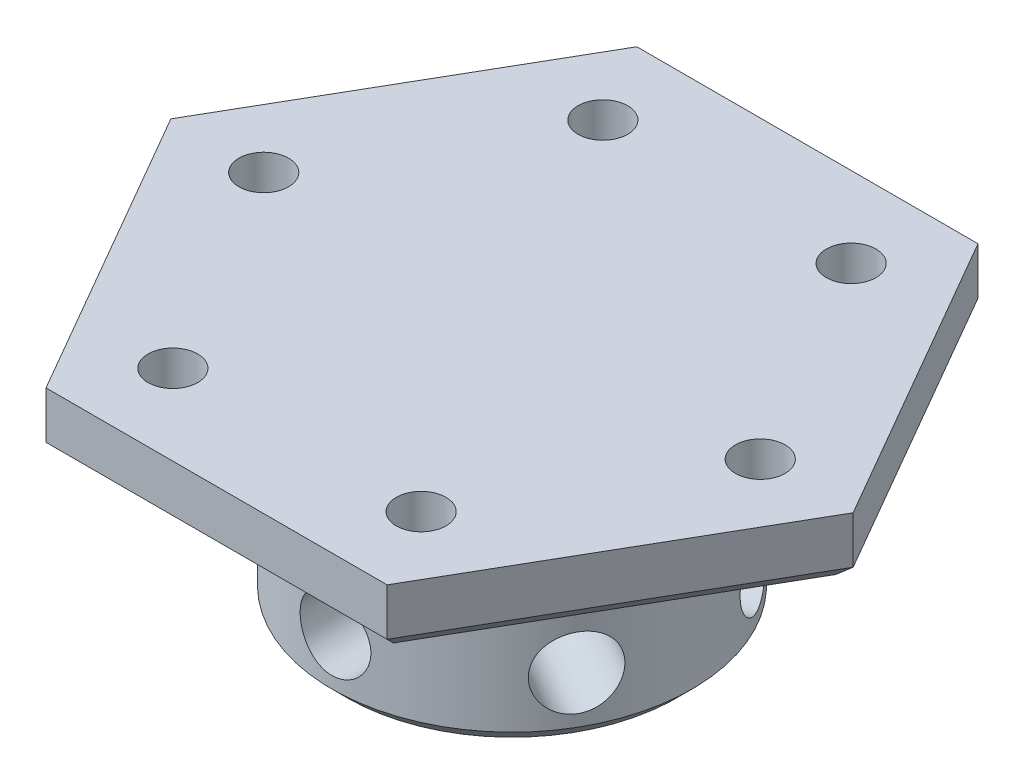
SolidWorks part; units mm, degrees
ref_plane "前视基准面" through (0, 0, 0) normal (0, 0, 1) x (1, 0, 0)
ref_plane "上视基准面" through (0, 0, 0) normal (0, 1, 0) x (1, 0, 0)
ref_plane "右视基准面" through (0, 0, 0) normal (1, 0, 0) x (0, 0, -1)
other "Configuration Table"
sketch "草图1" plane through (0, 0, 0) normal (0, 1, 0) x (1, 0, 0)
  line L1 (13.7409, 0) -> (6.8705, 11.9)
  line L2 (6.8705, 11.9) -> (-6.8705, 11.9)
  line L3 (-6.8705, 11.9) -> (-13.7409, 0)
  line L4 (-13.7409, 0) -> (-6.8705, -11.9)
  line L5 (-6.8705, -11.9) -> (6.8705, -11.9)
  line L6 (6.8705, -11.9) -> (13.7409, 0)
  circle A0 centre (0, 0) radius 11.9 construction
  dimension "D1" = 23.8
extrude "凸台-拉伸1" add sketch "草图1" along normal mid plane 2.5
sketch "草图2" plane through (0, -1.25, 0) normal (0, -1, 0) x (1, 0, 0)
  circle A0 centre (0, 0) radius 7.25
  dimension "D1" = 14.5
extrude "凸台-拉伸2" add sketch "草图2" along normal blind 7.5
sketch "草图3" plane through (-10.3057, 0, 5.95) normal (-0.866, 0, 0.5) x (0.5, 0, 0.866)
  line L0 (0, 3.3618) -> (0, -14.3234) construction
  line L1 (-7.25, -8.75) -> (7.25, -8.75) construction
  circle A0 centre (0, -6.25) radius 1.425
  dimension "D1" = 2.85
  dimension "D2" = 2.5
extrude "切除-拉伸1" cut sketch "草图3" against normal through all
pattern_circular "阵列(圆周)1" count 3 every 120 about axis through (0, -8.75, 0) along (0, -1, 0) of "切除-拉伸1"
chamfer "倒角1" distance 0.6 angle 45 7 edges at (0, -8.75, -7.25) (10.3057, -1.25, 5.95) (10.3057, -1.25, -5.95) (0, -1.25, -11.9) (-10.3057, -1.25, -5.95) (0, -1.25, 11.9) (-10.3057, -1.25, 5.95)
sketch "草图4" plane through (0, 1.25, 0) normal (0, 1, 0) x (1, 0, 0)
  line L0 (0, 0) -> (6.8705, 11.9) construction
  circle A0 centre (5, 8.6603) radius 1
  circle A1 centre (10, 0) radius 1
  circle A2 centre (5, -8.6603) radius 1
  circle A3 centre (-5, -8.6603) radius 1
  circle A4 centre (-10, 0) radius 1
  circle A5 centre (-5, 8.6603) radius 1
  point P19 (0, 0)
  dimension "D1" = 10
  dimension "D2" = 2
  dimension "D3" = 6
extrude "切除-拉伸2" cut sketch "草图4" against normal through all
